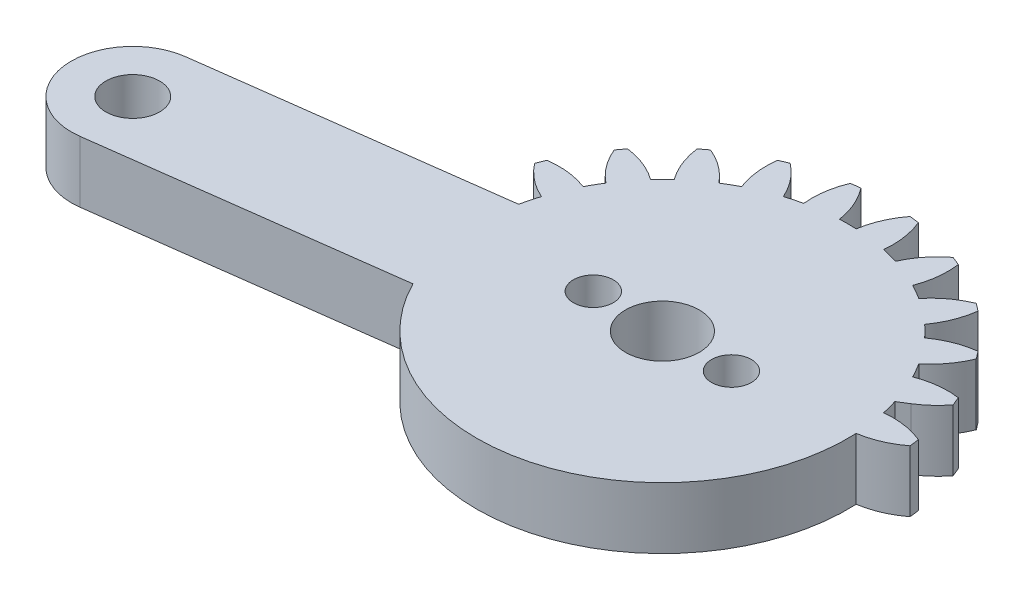
SolidWorks part; units mm, degrees
ref_plane "Front Plane" through (0, 0, 0) normal (0, 0, 1) x (1, 0, 0)
ref_plane "Top Plane" through (0, 0, 0) normal (0, 1, 0) x (1, 0, 0)
ref_plane "Right Plane" through (0, 0, 0) normal (1, 0, 0) x (0, 0, -1)
sketch "Sketch1" plane through (0, 0, 0) normal (0, 1, 0) x (1, 0, 0)
  line L0 (20.6437, 4) -> (2.0816, 4)
  line L1 (2.0816, -4) -> (20.6437, -4)
  arc A0 (2.0816, 4) -> (3.5217, 5.3071) centre (-0.7683, 8.5867) ccw
  arc A1 (3.5217, 5.3071) -> (3.2829, 5.8838) centre (-10.1063, 0) ccw
  arc A2 (3.2829, 5.8838) -> (0.6271, 5.5703) centre (2.5684, 0.5313) ccw
  arc A3 (0.6271, 5.5703) -> (0.0844, 6.5103) centre (-10.1063, 0) ccw
  arc A4 (0.0844, 6.5103) -> (1.6838, 8.6535) centre (-3.3089, 10.711) ccw
  arc A5 (1.6838, 8.6535) -> (1.3038, 9.1487) centre (-10.1063, 0) ccw
  arc A6 (1.3038, 9.1487) -> (-1.1803, 8.1585) centre (1.999, 3.7936) ccw
  arc A7 (-1.1803, 8.1585) -> (-1.9479, 8.926) centre (-10.1063, 0) ccw
  arc A8 (-1.9479, 8.926) -> (-0.9576, 11.4102) centre (-6.3127, 12.1053) ccw
  arc A9 (-0.9576, 11.4102) -> (-1.4528, 11.7901) centre (-10.1063, 0) ccw
  arc A10 (-1.4528, 11.7901) -> (-3.596, 10.1907) centre (0.6046, 6.7975) ccw
  arc A11 (-3.596, 10.1907) -> (-4.5361, 10.7334) centre (-10.1063, 0) ccw
  arc A12 (-4.5361, 10.7334) -> (-4.2225, 13.3892) centre (-9.5751, 12.6747) ccw
  arc A13 (-4.2225, 13.3892) -> (-4.7992, 13.6281) centre (-10.1063, 0) ccw
  arc A14 (-4.7992, 13.6281) -> (-6.4554, 11.5285) centre (-1.5196, 9.3381) ccw
  arc A15 (-6.4554, 11.5285) -> (-7.5039, 11.8094) centre (-10.1063, 0) ccw
  arc A16 (-7.5039, 11.8094) -> (-7.8884, 14.4558) centre (-12.8736, 12.3803) ccw
  arc A17 (-7.8884, 14.4558) -> (-8.5072, 14.5373) centre (-10.1063, 0) ccw
  arc A18 (-8.5072, 14.5373) -> (-9.5636, 12.0806) centre (-4.2291, 11.2423) ccw
  arc A19 (-9.5636, 12.0806) -> (-10.6491, 12.0806) centre (-10.1063, 0) ccw
  arc A20 (-10.6491, 12.0806) -> (-11.7054, 14.5373) centre (-15.9836, 11.2423) ccw
  arc A21 (-11.7054, 14.5373) -> (-12.3243, 14.4558) centre (-10.1063, 0) ccw
  arc A22 (-12.3243, 14.4558) -> (-12.7088, 11.8094) centre (-7.3391, 12.3803) ccw
  arc A23 (-12.7088, 11.8094) -> (-13.7573, 11.5285) centre (-10.1063, 0) ccw
  arc A24 (-13.7573, 11.5285) -> (-15.4135, 13.6281) centre (-18.6931, 9.3381) ccw
  arc A25 (-15.4135, 13.6281) -> (-15.9901, 13.3892) centre (-10.1063, 0) ccw
  arc A26 (-15.9901, 13.3892) -> (-15.6766, 10.7334) centre (-10.6376, 12.6747) ccw
  arc A27 (-15.6766, 10.7334) -> (-16.6166, 10.1907) centre (-10.1063, 0) ccw
  arc A28 (-16.6166, 10.1907) -> (-18.7599, 11.7901) centre (-20.8173, 6.7975) ccw
  arc A29 (-18.7599, 11.7901) -> (-19.255, 11.4102) centre (-10.1063, 0) ccw
  arc A30 (-19.255, 11.4102) -> (-18.2648, 8.926) centre (-13.9, 12.1053) ccw
  arc A31 (-18.2648, 8.926) -> (-19.0324, 8.1585) centre (-10.1063, 0) ccw
  arc A32 (-19.0324, 8.1585) -> (-21.5165, 9.1487) centre (-22.2117, 3.7936) ccw
  arc A33 (-21.5165, 9.1487) -> (-21.8965, 8.6535) centre (-10.1063, 0) ccw
  arc A34 (-21.8965, 8.6535) -> (-20.2971, 6.5103) centre (-16.9038, 10.711) ccw
  arc A35 (-20.2971, 6.5103) -> (-20.8398, 5.5703) centre (-10.1063, 0) ccw
  arc A36 (-20.8398, 5.5703) -> (-23.4956, 5.8838) centre (-22.7811, 0.5313) ccw
  arc A37 (-23.4956, 5.8838) -> (-23.7344, 5.3071) centre (-10.1063, 0) ccw
  arc A38 (-23.7344, 5.3071) -> (-21.6348, 3.6509) centre (-19.4444, 8.5867) ccw
  arc A39 (-21.6348, 3.6509) -> (-21.9157, 2.6025) centre (-10.1063, 0) ccw
  arc A40 (-21.9157, 2.6025) -> (-24.5622, 2.2179) centre (-22.4867, -2.7673) ccw
  arc A41 (-24.5622, 2.2179) -> (-24.6437, 1.5991) centre (-10.1063, 0) ccw
  arc A42 (-24.6437, 1.5991) -> (-22.1869, 0.5427) centre (-21.3486, 5.8773) ccw
  arc A43 (-22.1869, 0.5427) -> (-22.1869, -0.5427) centre (-10.1063, 0) ccw
  arc A44 (-22.1869, -0.5427) -> (-24.6437, -1.5991) centre (-21.3486, -5.8773) ccw
  arc A45 (-24.6437, -1.5991) -> (-24.5622, -2.2179) centre (-10.1063, 0) ccw
  arc A46 (-24.5622, -2.2179) -> (-21.9157, -2.6025) centre (-22.4867, 2.7673) ccw
  arc A47 (-21.9157, -2.6025) -> (-21.6348, -3.6509) centre (-10.1063, 0) ccw
  arc A48 (-21.6348, -3.6509) -> (-23.7344, -5.3071) centre (-19.4444, -8.5867) ccw
  arc A49 (-23.7344, -5.3071) -> (-23.4956, -5.8838) centre (-10.1063, 0) ccw
  arc A50 (-23.4956, -5.8838) -> (-20.8398, -5.5703) centre (-22.7811, -0.5313) ccw
  arc A51 (-20.8398, -5.5703) -> (-20.2971, -6.5103) centre (-10.1063, 0) ccw
  arc A52 (-20.2971, -6.5103) -> (-21.8965, -8.6535) centre (-16.9038, -10.711) ccw
  arc A53 (-21.8965, -8.6535) -> (-21.5165, -9.1487) centre (-10.1063, 0) ccw
  arc A54 (-21.5165, -9.1487) -> (-19.0324, -8.1585) centre (-22.2117, -3.7936) ccw
  arc A55 (-19.0324, -8.1585) -> (-18.2648, -8.926) centre (-10.1063, 0) ccw
  arc A56 (-18.2648, -8.926) -> (-19.255, -11.4102) centre (-13.9, -12.1053) ccw
  arc A57 (-19.255, -11.4102) -> (-18.7599, -11.7901) centre (-10.1063, 0) ccw
  arc A58 (-18.7599, -11.7901) -> (-16.6166, -10.1907) centre (-20.8173, -6.7975) ccw
  arc A59 (-16.6166, -10.1907) -> (-15.6766, -10.7334) centre (-10.1063, 0) ccw
  arc A60 (-15.6766, -10.7334) -> (-15.9901, -13.3892) centre (-10.6376, -12.6747) ccw
  arc A61 (-15.9901, -13.3892) -> (-15.4135, -13.6281) centre (-10.1063, 0) ccw
  arc A62 (-15.4135, -13.6281) -> (-13.7573, -11.5285) centre (-18.6931, -9.3381) ccw
  arc A63 (-13.7573, -11.5285) -> (-12.7088, -11.8094) centre (-10.1063, 0) ccw
  arc A64 (-12.7088, -11.8094) -> (-12.3243, -14.4558) centre (-7.3391, -12.3803) ccw
  arc A65 (-12.3243, -14.4558) -> (-11.7054, -14.5373) centre (-10.1063, 0) ccw
  arc A66 (-11.7054, -14.5373) -> (-10.6491, -12.0806) centre (-15.9836, -11.2423) ccw
  arc A67 (-10.6491, -12.0806) -> (-9.5636, -12.0806) centre (-10.1063, 0) ccw
  arc A68 (-9.5636, -12.0806) -> (-8.5072, -14.5373) centre (-4.2291, -11.2423) ccw
  arc A69 (-8.5072, -14.5373) -> (-7.8884, -14.4558) centre (-10.1063, 0) ccw
  arc A70 (-7.8884, -14.4558) -> (-7.5039, -11.8094) centre (-12.8736, -12.3803) ccw
  arc A71 (-7.5039, -11.8094) -> (-6.4554, -11.5285) centre (-10.1063, 0) ccw
  arc A72 (-6.4554, -11.5285) -> (-4.7992, -13.6281) centre (-1.5196, -9.3381) ccw
  arc A73 (-4.7992, -13.6281) -> (-4.2225, -13.3892) centre (-10.1063, 0) ccw
  arc A74 (-4.2225, -13.3892) -> (-4.5361, -10.7334) centre (-9.5751, -12.6747) ccw
  arc A75 (-4.5361, -10.7334) -> (-3.596, -10.1907) centre (-10.1063, 0) ccw
  arc A76 (-3.596, -10.1907) -> (-1.4528, -11.7901) centre (0.6046, -6.7975) ccw
  arc A77 (-1.4528, -11.7901) -> (-0.9576, -11.4102) centre (-10.1063, 0) ccw
  arc A78 (-0.9576, -11.4102) -> (-1.9479, -8.926) centre (-6.3127, -12.1053) ccw
  arc A79 (-1.9479, -8.926) -> (-1.1803, -8.1585) centre (-10.1063, 0) ccw
  arc A80 (-1.1803, -8.1585) -> (1.3038, -9.1487) centre (1.999, -3.7936) ccw
  arc A81 (1.3038, -9.1487) -> (1.6838, -8.6535) centre (-10.1063, 0) ccw
  arc A82 (1.6838, -8.6535) -> (0.0844, -6.5103) centre (-3.3089, -10.711) ccw
  arc A83 (0.0844, -6.5103) -> (0.6271, -5.5703) centre (-10.1063, 0) ccw
  arc A84 (0.6271, -5.5703) -> (3.2829, -5.8838) centre (2.5684, -0.5313) ccw
  arc A85 (3.2829, -5.8838) -> (3.5217, -5.3071) centre (-10.1063, 0) ccw
  arc A86 (3.5217, -5.3071) -> (2.0816, -4) centre (-0.7683, -8.5867) ccw
  arc A87 (20.6437, -4) -> (20.6437, 4) centre (20.6437, 0) ccw
  circle A88 centre (-10.1063, 0) radius 1.5
  circle A89 centre (20.6437, 0) radius 1.5
  dimension "D1" = 3
  dimension "D2" = 3
extrude "Boss-Extrude1" add sketch "Sketch1" along normal blind 4
sketch "Sketch3" plane through (0, 4, 0) normal (0, 1, 0) x (1, 0, 0)
  line L0 (-10.1063, 0) -> (-40.8563, 0) construction
  line L1 (-10.1063, 0) -> (-40.5933, -4.0137)
  line L2 (-10.6284, 3.9658) -> (-41.1154, -0.0479)
  line L3 (-9.5842, -3.9658) -> (-40.0712, -7.9795)
  line L4 (-10.1063, 0) -> (-4.5096, 13.5117) construction
  line L5 (-10.1063, 0) -> (-8.1974, 14.4999) construction
  circle A0 centre (-10.1063, 0) radius 1.5
  circle A1 centre (20.6437, 0) radius 1.5 construction
  circle A2 centre (20.6437, 0) radius 1.5
  circle A3 centre (-40.5933, -4.0137) radius 1.75
  circle A4 centre (-40.5933, -4.0137) radius 4
  circle A5 centre (-10.1063, 0) radius 4
  arc A6 (-4.2225, 13.3892) -> (-4.7992, 13.6281) centre (-10.1063, 0) ccw construction
  arc A7 (-7.8884, 14.4558) -> (-8.5072, 14.5373) centre (-10.1063, 0) ccw construction
  dimension "D2" = 3
  dimension "D5" = 3.5
  dimension "D6" = 8
  dimension "D7" = 8
  dimension "D1" = 30.75
  dimension "D4" = 7.5
extrude "Boss-Extrude2" add sketch "Sketch3" against normal blind 4 contours L0 A5 L2 | A5 L0 L2 A4 L1 | A4 A3 | A5 L1 A4 L3 | L0 A0 L1 A5 | A0 L0 A5 L1 region at (-13.19, 4, -2.3662) region at (-25.0786, 4, 4.0667) region at (-25.621, 4, -0.053) region at (-36.7147, 4, 3.7595)
sketch "Sketch4" plane through (0, 4, 0) normal (0, 1, 0) x (1, 0, 0)
  line L0 (20.6437, 4) -> (2.0816, 4) construction
  line L1 (2.0816, -4) -> (20.6437, -4) construction
  line L2 (20.6437, 4) -> (2.0816, 4)
  line L3 (2.0816, -4) -> (20.6437, -4)
  line L4 (2.0816, 4) -> (1.4381, 3.6001)
  line L5 (-21.6245, -5.5509) -> (-20.8986, -5.4553)
  line L6 (-10.1063, 0) -> (0.0844, 6.5103) construction
  line L7 (-10.1063, 0) -> (1.9742, 0.5427) construction
  line L8 (-24.5755, 2.1296) -> (-41.1154, -0.0479)
  line L9 (-40.0712, -7.9795) -> (-23.5312, -5.8019)
  line L10 (2.0816, -4) -> (20.6437, -4)
  line L11 (20.6437, 4) -> (2.0816, 4)
  line L12 (-21.9429, 2.4762) -> (-41.1154, -0.0479)
  line L13 (-40.0712, -7.9795) -> (-21.6245, -5.5509)
  line L14 (2.0816, -4) -> (20.6437, -4)
  line L15 (20.6437, 4) -> (2.0816, 4)
  circle A0 centre (-10.1063, 0) radius 12.0927
  arc A1 (3.2829, 5.8838) -> (0.6271, 5.5703) centre (2.5684, 0.5313) ccw construction
  arc A2 (3.5217, 5.3071) -> (3.2829, 5.8838) centre (-10.1063, 0) ccw construction
  arc A3 (2.0816, 4) -> (3.5217, 5.3071) centre (-0.7683, 8.5867) ccw construction
  arc A4 (20.6437, -4) -> (20.6437, 4) centre (20.6437, 0) ccw construction
  arc A5 (3.5217, -5.3071) -> (2.0816, -4) centre (-0.7683, -8.5867) ccw construction
  arc A6 (3.2829, -5.8838) -> (3.5217, -5.3071) centre (-10.1063, 0) ccw construction
  arc A7 (0.6271, -5.5703) -> (3.2829, -5.8838) centre (2.5684, -0.5313) ccw construction
  arc A8 (3.2829, 5.8838) -> (0.6271, 5.5703) centre (2.5684, 0.5313) ccw
  arc A9 (3.5217, 5.3071) -> (3.2829, 5.8838) centre (-10.1063, 0) ccw
  arc A10 (2.0816, 4) -> (3.5217, 5.3071) centre (-0.7683, 8.5867) ccw
  arc A11 (20.6437, -4) -> (20.6437, 4) centre (20.6437, 0) ccw
  arc A12 (3.5217, -5.3071) -> (2.0816, -4) centre (-0.7683, -8.5867) ccw
  arc A13 (3.2829, -5.8838) -> (3.5217, -5.3071) centre (-10.1063, 0) ccw
  arc A14 (0.6271, -5.5703) -> (3.2829, -5.8838) centre (2.5684, -0.5313) ccw
  arc A15 (1.9742, 0.5427) -> (4.431, 1.5991) centre (1.1359, 5.8773) ccw
  arc A16 (4.3495, 2.2179) -> (1.7031, 2.6025) centre (2.274, -2.7673) ccw
  arc A17 (4.431, 1.5991) -> (4.3495, 2.2179) centre (-10.1063, 0) ccw
  arc A95 (-21.6348, 3.6509) -> (-21.9157, 2.6025) centre (-10.1063, 0) ccw
  arc A96 (-41.1154, -0.0479) -> (-40.0712, -7.9795) centre (-40.5933, -4.0137) ccw
  arc A97 (-20.2971, -6.5103) -> (-21.8965, -8.6535) centre (-16.9038, -10.711) ccw
  arc A98 (-21.8965, -8.6535) -> (-21.5165, -9.1487) centre (-10.1063, 0) ccw
  arc A99 (-21.5165, -9.1487) -> (-19.0324, -8.1585) centre (-22.2117, -3.7936) ccw
  arc A100 (-19.0324, -8.1585) -> (-18.2648, -8.926) centre (-10.1063, 0) ccw
  arc A101 (-18.2648, -8.926) -> (-19.255, -11.4102) centre (-13.9, -12.1053) ccw
  arc A102 (-19.255, -11.4102) -> (-18.7599, -11.7901) centre (-10.1063, 0) ccw
  arc A103 (-18.7599, -11.7901) -> (-16.6166, -10.1907) centre (-20.8173, -6.7975) ccw
  arc A104 (-16.6166, -10.1907) -> (-15.6766, -10.7334) centre (-10.1063, 0) ccw
  arc A105 (-15.6766, -10.7334) -> (-15.9901, -13.3892) centre (-10.6376, -12.6747) ccw
  arc A106 (-15.9901, -13.3892) -> (-15.4135, -13.6281) centre (-10.1063, 0) ccw
  arc A107 (-15.4135, -13.6281) -> (-13.7573, -11.5285) centre (-18.6931, -9.3381) ccw
  arc A108 (-13.7573, -11.5285) -> (-12.7088, -11.8094) centre (-10.1063, 0) ccw
  arc A109 (-12.7088, -11.8094) -> (-12.3243, -14.4558) centre (-7.3391, -12.3803) ccw
  arc A110 (-12.3243, -14.4558) -> (-11.7054, -14.5373) centre (-10.1063, 0) ccw
  arc A111 (-11.7054, -14.5373) -> (-10.6491, -12.0806) centre (-15.9836, -11.2423) ccw
  arc A112 (-10.6491, -12.0806) -> (-9.5636, -12.0806) centre (-10.1063, 0) ccw
  arc A113 (-9.5636, -12.0806) -> (-8.5072, -14.5373) centre (-4.2291, -11.2423) ccw
  arc A114 (-8.5072, -14.5373) -> (-7.8884, -14.4558) centre (-10.1063, 0) ccw
  arc A115 (-7.8884, -14.4558) -> (-7.5039, -11.8094) centre (-12.8736, -12.3803) ccw
  arc A116 (-7.5039, -11.8094) -> (-6.4554, -11.5285) centre (-10.1063, 0) ccw
  arc A117 (-6.4554, -11.5285) -> (-4.7992, -13.6281) centre (-1.5196, -9.3381) ccw
  arc A118 (-4.7992, -13.6281) -> (-4.2225, -13.3892) centre (-10.1063, 0) ccw
  arc A119 (-4.2225, -13.3892) -> (-4.5361, -10.7334) centre (-9.5751, -12.6747) ccw
  arc A120 (-4.5361, -10.7334) -> (-3.596, -10.1907) centre (-10.1063, 0) ccw
  arc A121 (-3.596, -10.1907) -> (-1.4528, -11.7901) centre (0.6046, -6.7975) ccw
  arc A122 (-1.4528, -11.7901) -> (-0.9576, -11.4102) centre (-10.1063, 0) ccw
  arc A123 (-0.9576, -11.4102) -> (-1.9479, -8.926) centre (-6.3127, -12.1053) ccw
  arc A124 (-1.9479, -8.926) -> (-1.1803, -8.1585) centre (-10.1063, 0) ccw
  arc A125 (-1.1803, -8.1585) -> (1.3038, -9.1487) centre (1.999, -3.7936) ccw
  arc A126 (1.3038, -9.1487) -> (1.6838, -8.6535) centre (-10.1063, 0) ccw
  arc A127 (1.6838, -8.6535) -> (0.0844, -6.5103) centre (-3.3089, -10.711) ccw
  arc A128 (0.0844, -6.5103) -> (0.6271, -5.5703) centre (-10.1063, 0) ccw
  arc A129 (0.6271, -5.5703) -> (3.2829, -5.8838) centre (2.5684, -0.5313) ccw
  arc A130 (3.2829, -5.8838) -> (3.5217, -5.3071) centre (-10.1063, 0) ccw
  arc A131 (3.5217, -5.3071) -> (2.0816, -4) centre (-0.7683, -8.5867) ccw
  arc A132 (20.6437, -4) -> (20.6437, 4) centre (20.6437, 0) ccw
  arc A133 (2.0816, 4) -> (3.5217, 5.3071) centre (-0.7683, 8.5867) ccw
  arc A134 (3.5217, 5.3071) -> (3.2829, 5.8838) centre (-10.1063, 0) ccw
  arc A135 (3.2829, 5.8838) -> (0.6271, 5.5703) centre (2.5684, 0.5313) ccw
  arc A136 (0.6271, 5.5703) -> (0.0844, 6.5103) centre (-10.1063, 0) ccw
  arc A137 (0.0844, 6.5103) -> (1.6838, 8.6535) centre (-3.3089, 10.711) ccw
  arc A138 (1.6838, 8.6535) -> (1.3038, 9.1487) centre (-10.1063, 0) ccw
  arc A139 (1.3038, 9.1487) -> (-1.1803, 8.1585) centre (1.999, 3.7936) ccw
  arc A140 (-1.1803, 8.1585) -> (-1.9479, 8.926) centre (-10.1063, 0) ccw
  arc A141 (-1.9479, 8.926) -> (-0.9576, 11.4102) centre (-6.3127, 12.1053) ccw
  arc A142 (-0.9576, 11.4102) -> (-1.4528, 11.7901) centre (-10.1063, 0) ccw
  arc A143 (-1.4528, 11.7901) -> (-3.596, 10.1907) centre (0.6046, 6.7975) ccw
  arc A144 (-3.596, 10.1907) -> (-4.5361, 10.7334) centre (-10.1063, 0) ccw
  arc A145 (-4.5361, 10.7334) -> (-4.2225, 13.3892) centre (-9.5751, 12.6747) ccw
  arc A146 (-4.2225, 13.3892) -> (-4.7992, 13.6281) centre (-10.1063, 0) ccw
  arc A147 (-4.7992, 13.6281) -> (-6.4554, 11.5285) centre (-1.5196, 9.3381) ccw
  arc A148 (-6.4554, 11.5285) -> (-7.5039, 11.8094) centre (-10.1063, 0) ccw
  arc A149 (-7.5039, 11.8094) -> (-7.8884, 14.4558) centre (-12.8736, 12.3803) ccw
  arc A150 (-7.8884, 14.4558) -> (-8.5072, 14.5373) centre (-10.1063, 0) ccw
  arc A151 (-8.5072, 14.5373) -> (-9.5636, 12.0806) centre (-4.2291, 11.2423) ccw
  arc A152 (-9.5636, 12.0806) -> (-10.6491, 12.0806) centre (-10.1063, 0) ccw
  arc A153 (-10.6491, 12.0806) -> (-11.7054, 14.5373) centre (-15.9836, 11.2423) ccw
  arc A154 (-11.7054, 14.5373) -> (-12.3243, 14.4558) centre (-10.1063, 0) ccw
  arc A155 (-12.3243, 14.4558) -> (-12.7088, 11.8094) centre (-7.3391, 12.3803) ccw
  arc A156 (-12.7088, 11.8094) -> (-13.7573, 11.5285) centre (-10.1063, 0) ccw
  arc A157 (-13.7573, 11.5285) -> (-15.4135, 13.6281) centre (-18.6931, 9.3381) ccw
  arc A158 (-15.4135, 13.6281) -> (-15.9901, 13.3892) centre (-10.1063, 0) ccw
  arc A159 (-15.9901, 13.3892) -> (-15.6766, 10.7334) centre (-10.6376, 12.6747) ccw
  arc A160 (-15.6766, 10.7334) -> (-16.6166, 10.1907) centre (-10.1063, 0) ccw
  arc A161 (-16.6166, 10.1907) -> (-18.7599, 11.7901) centre (-20.8173, 6.7975) ccw
  arc A162 (-18.7599, 11.7901) -> (-19.255, 11.4102) centre (-10.1063, 0) ccw
  arc A163 (-19.255, 11.4102) -> (-18.2648, 8.926) centre (-13.9, 12.1053) ccw
  arc A164 (-18.2648, 8.926) -> (-19.0324, 8.1585) centre (-10.1063, 0) ccw
  arc A165 (-19.0324, 8.1585) -> (-21.5165, 9.1487) centre (-22.2117, 3.7936) ccw
  arc A166 (-21.5165, 9.1487) -> (-21.8965, 8.6535) centre (-10.1063, 0) ccw
  arc A167 (-21.8965, 8.6535) -> (-20.2971, 6.5103) centre (-16.9038, 10.711) ccw
  arc A168 (-20.2971, 6.5103) -> (-20.8398, 5.5703) centre (-10.1063, 0) ccw
  arc A169 (-20.8398, 5.5703) -> (-23.4956, 5.8838) centre (-22.7811, 0.5313) ccw
  arc A170 (-23.4956, 5.8838) -> (-23.7344, 5.3071) centre (-10.1063, 0) ccw
  arc A171 (-23.7344, 5.3071) -> (-21.6348, 3.6509) centre (-19.4444, 8.5867) ccw
  arc A172 (-21.6348, 3.6509) -> (-21.9157, 2.6025) centre (-10.1063, 0) ccw
  arc A175 (-23.4956, -5.8838) -> (-20.8398, -5.5703) centre (-22.7811, -0.5313) ccw
  arc A176 (-41.1154, -0.0479) -> (-40.0712, -7.9795) centre (-40.5933, -4.0137) ccw
  arc A177 (-20.2971, -6.5103) -> (-21.8965, -8.6535) centre (-16.9038, -10.711) ccw
  arc A178 (-21.8965, -8.6535) -> (-21.5165, -9.1487) centre (-10.1063, 0) ccw
  arc A179 (-21.5165, -9.1487) -> (-19.0324, -8.1585) centre (-22.2117, -3.7936) ccw
  arc A180 (-19.0324, -8.1585) -> (-18.2648, -8.926) centre (-10.1063, 0) ccw
  arc A181 (-18.2648, -8.926) -> (-19.255, -11.4102) centre (-13.9, -12.1053) ccw
  arc A182 (-19.255, -11.4102) -> (-18.7599, -11.7901) centre (-10.1063, 0) ccw
  arc A183 (-18.7599, -11.7901) -> (-16.6166, -10.1907) centre (-20.8173, -6.7975) ccw
  arc A184 (-16.6166, -10.1907) -> (-15.6766, -10.7334) centre (-10.1063, 0) ccw
  arc A185 (-15.6766, -10.7334) -> (-15.9901, -13.3892) centre (-10.6376, -12.6747) ccw
  arc A186 (-15.9901, -13.3892) -> (-15.4135, -13.6281) centre (-10.1063, 0) ccw
  arc A187 (-15.4135, -13.6281) -> (-13.7573, -11.5285) centre (-18.6931, -9.3381) ccw
  arc A188 (-13.7573, -11.5285) -> (-12.7088, -11.8094) centre (-10.1063, 0) ccw
  arc A189 (-12.7088, -11.8094) -> (-12.3243, -14.4558) centre (-7.3391, -12.3803) ccw
  arc A190 (-12.3243, -14.4558) -> (-11.7054, -14.5373) centre (-10.1063, 0) ccw
  arc A191 (-11.7054, -14.5373) -> (-10.6491, -12.0806) centre (-15.9836, -11.2423) ccw
  arc A192 (-10.6491, -12.0806) -> (-9.5636, -12.0806) centre (-10.1063, 0) ccw
  arc A193 (-9.5636, -12.0806) -> (-8.5072, -14.5373) centre (-4.2291, -11.2423) ccw
  arc A194 (-8.5072, -14.5373) -> (-7.8884, -14.4558) centre (-10.1063, 0) ccw
  arc A195 (-7.8884, -14.4558) -> (-7.5039, -11.8094) centre (-12.8736, -12.3803) ccw
  arc A196 (-7.5039, -11.8094) -> (-6.4554, -11.5285) centre (-10.1063, 0) ccw
  arc A197 (-6.4554, -11.5285) -> (-4.7992, -13.6281) centre (-1.5196, -9.3381) ccw
  arc A198 (-4.7992, -13.6281) -> (-4.2225, -13.3892) centre (-10.1063, 0) ccw
  arc A199 (-4.2225, -13.3892) -> (-4.5361, -10.7334) centre (-9.5751, -12.6747) ccw
  arc A200 (-4.5361, -10.7334) -> (-3.596, -10.1907) centre (-10.1063, 0) ccw
  arc A201 (-3.596, -10.1907) -> (-1.4528, -11.7901) centre (0.6046, -6.7975) ccw
  arc A202 (-1.4528, -11.7901) -> (-0.9576, -11.4102) centre (-10.1063, 0) ccw
  arc A203 (-0.9576, -11.4102) -> (-1.9479, -8.926) centre (-6.3127, -12.1053) ccw
  arc A204 (-1.9479, -8.926) -> (-1.1803, -8.1585) centre (-10.1063, 0) ccw
  arc A205 (-1.1803, -8.1585) -> (1.3038, -9.1487) centre (1.999, -3.7936) ccw
  arc A206 (1.3038, -9.1487) -> (1.6838, -8.6535) centre (-10.1063, 0) ccw
  arc A207 (1.6838, -8.6535) -> (0.0844, -6.5103) centre (-3.3089, -10.711) ccw
  arc A208 (0.0844, -6.5103) -> (0.6271, -5.5703) centre (-10.1063, 0) ccw
  arc A209 (0.6271, -5.5703) -> (3.2829, -5.8838) centre (2.5684, -0.5313) ccw
  arc A210 (3.2829, -5.8838) -> (3.5217, -5.3071) centre (-10.1063, 0) ccw
  arc A211 (3.5217, -5.3071) -> (2.0816, -4) centre (-0.7683, -8.5867) ccw
  arc A212 (20.6437, -4) -> (20.6437, 4) centre (20.6437, 0) ccw
  arc A213 (2.0816, 4) -> (3.5217, 5.3071) centre (-0.7683, 8.5867) ccw
  arc A214 (3.5217, 5.3071) -> (3.2829, 5.8838) centre (-10.1063, 0) ccw
  arc A215 (3.2829, 5.8838) -> (0.6271, 5.5703) centre (2.5684, 0.5313) ccw
  arc A216 (0.6271, 5.5703) -> (0.0844, 6.5103) centre (-10.1063, 0) ccw
  arc A217 (0.0844, 6.5103) -> (1.6838, 8.6535) centre (-3.3089, 10.711) ccw
  arc A218 (1.6838, 8.6535) -> (1.3038, 9.1487) centre (-10.1063, 0) ccw
  arc A219 (1.3038, 9.1487) -> (-1.1803, 8.1585) centre (1.999, 3.7936) ccw
  arc A220 (-1.1803, 8.1585) -> (-1.9479, 8.926) centre (-10.1063, 0) ccw
  arc A221 (-1.9479, 8.926) -> (-0.9576, 11.4102) centre (-6.3127, 12.1053) ccw
  arc A222 (-0.9576, 11.4102) -> (-1.4528, 11.7901) centre (-10.1063, 0) ccw
  arc A223 (-1.4528, 11.7901) -> (-3.596, 10.1907) centre (0.6046, 6.7975) ccw
  arc A224 (-3.596, 10.1907) -> (-4.5361, 10.7334) centre (-10.1063, 0) ccw
  arc A225 (-4.5361, 10.7334) -> (-4.2225, 13.3892) centre (-9.5751, 12.6747) ccw
  arc A226 (-4.2225, 13.3892) -> (-4.7992, 13.6281) centre (-10.1063, 0) ccw
  arc A227 (-4.7992, 13.6281) -> (-6.4554, 11.5285) centre (-1.5196, 9.3381) ccw
  arc A228 (-6.4554, 11.5285) -> (-7.5039, 11.8094) centre (-10.1063, 0) ccw
  arc A229 (-7.5039, 11.8094) -> (-7.8884, 14.4558) centre (-12.8736, 12.3803) ccw
  arc A230 (-7.8884, 14.4558) -> (-8.5072, 14.5373) centre (-10.1063, 0) ccw
  arc A231 (-8.5072, 14.5373) -> (-9.5636, 12.0806) centre (-4.2291, 11.2423) ccw
  arc A232 (-9.5636, 12.0806) -> (-10.6491, 12.0806) centre (-10.1063, 0) ccw
  arc A233 (-10.6491, 12.0806) -> (-11.7054, 14.5373) centre (-15.9836, 11.2423) ccw
  arc A234 (-11.7054, 14.5373) -> (-12.3243, 14.4558) centre (-10.1063, 0) ccw
  arc A235 (-12.3243, 14.4558) -> (-12.7088, 11.8094) centre (-7.3391, 12.3803) ccw
  arc A236 (-12.7088, 11.8094) -> (-13.7573, 11.5285) centre (-10.1063, 0) ccw
  arc A237 (-13.7573, 11.5285) -> (-15.4135, 13.6281) centre (-18.6931, 9.3381) ccw
  arc A238 (-15.4135, 13.6281) -> (-15.9901, 13.3892) centre (-10.1063, 0) ccw
  arc A239 (-15.9901, 13.3892) -> (-15.6766, 10.7334) centre (-10.6376, 12.6747) ccw
  arc A240 (-15.6766, 10.7334) -> (-16.6166, 10.1907) centre (-10.1063, 0) ccw
  arc A241 (-16.6166, 10.1907) -> (-18.7599, 11.7901) centre (-20.8173, 6.7975) ccw
  arc A242 (-18.7599, 11.7901) -> (-19.255, 11.4102) centre (-10.1063, 0) ccw
  arc A243 (-19.255, 11.4102) -> (-18.2648, 8.926) centre (-13.9, 12.1053) ccw
  arc A244 (-18.2648, 8.926) -> (-19.0324, 8.1585) centre (-10.1063, 0) ccw
  arc A245 (-19.0324, 8.1585) -> (-21.5165, 9.1487) centre (-22.2117, 3.7936) ccw
  arc A246 (-21.5165, 9.1487) -> (-21.8965, 8.6535) centre (-10.1063, 0) ccw
  arc A247 (-21.8965, 8.6535) -> (-20.2971, 6.5103) centre (-16.9038, 10.711) ccw
  arc A248 (-20.2971, 6.5103) -> (-20.8398, 5.5703) centre (-10.1063, 0) ccw
  arc A249 (-20.8398, 5.5703) -> (-23.4956, 5.8838) centre (-22.7811, 0.5313) ccw
  arc A250 (-23.4956, 5.8838) -> (-23.7344, 5.3071) centre (-10.1063, 0) ccw
  arc A251 (-23.7344, 5.3071) -> (-21.6348, 3.6509) centre (-19.4444, 8.5867) ccw
  arc A252 (-23.4956, -5.8838) -> (-20.8398, -5.5703) centre (-22.7811, -0.5313) ccw
  arc A253 (-20.8398, -5.5703) -> (-20.2971, -6.5103) centre (-10.1063, 0) ccw
  arc A254 (-20.8398, -5.5703) -> (-20.2971, -6.5103) centre (-10.1063, 0) ccw
  arc A255 (-23.5312, -5.8019) -> (-23.4956, -5.8838) centre (-10.1063, 0) ccw
  arc A256 (-23.5312, -5.8019) -> (-23.4956, -5.8838) centre (-10.1063, 0) ccw
  arc A257 (-21.9157, 2.6025) -> (-24.5622, 2.2179) centre (-22.4867, -2.7673) ccw
  arc A258 (-21.9157, 2.6025) -> (-24.5622, 2.2179) centre (-22.4867, -2.7673) ccw
  arc A259 (-24.5622, 2.2179) -> (-24.5755, 2.1296) centre (-10.1063, 0) ccw
  arc A260 (-24.5622, 2.2179) -> (-24.5755, 2.1296) centre (-10.1063, 0) ccw
  point P40 (-10.1063, 0)
  dimension "D2" = 24.1855
  dimension "D4" = 30
  dimension "D1" = 0
  dimension "D3" = 2
extrude "Cut-Extrude1" cut sketch "Sketch4" against normal blind 4 contours A178 A179 A0 L5 A177 | A182 A183 A0 A181 | A186 A187 A0 A185 | A190 A191 A0 A189 | A194 A195 A0 A193 | A198 A199 A0 A197 | A202 A203 A0 A201 | A206 A207 A0 A205 | A258 A260 L12 A0 | L13 A256 A252 A0 L5 | A0 A14 A13 A12 L3 A11 L2 L4 region at (12.7894, 4, 0.1545) region at (0.3325, 4, 8.01) region at (-2.0963, 4, 10.4389) region at (-5.071, 4, 12.1563) region at (-8.3889, 4, 13.0454) region at (-11.8238, 4, 13.0454) region at (-15.1417, 4, 12.1563) region at (-18.1164, 4, 10.4389) region at (-20.5452, 4, 8.01) region at (-23.2126, 4, -2.4243) region at (-22.1386, 4, 5.7339)
sketch "Sketch5" plane through (0, 4, 0) normal (0, 1, 0) x (1, 0, 0)
  circle A0 centre (-10.1063, 0) radius 2.4
  circle A1 centre (-5.6063, 0) radius 1.3
  circle A2 centre (-14.6063, 0) radius 1.3
  circle A3 centre (-10.1063, 0) radius 1.5 construction
  dimension "D1" = 4.8
  dimension "D2" = 2.6
  dimension "D3" = 2.6
  dimension "D4" = 4.5
  dimension "D5" = 9
extrude "Cut-Extrude2" cut sketch "Sketch5" against normal up to next contours A2 | A1 | A0 region at (-5.6063, 4, 0) region at (-14.6063, 4, 0)
